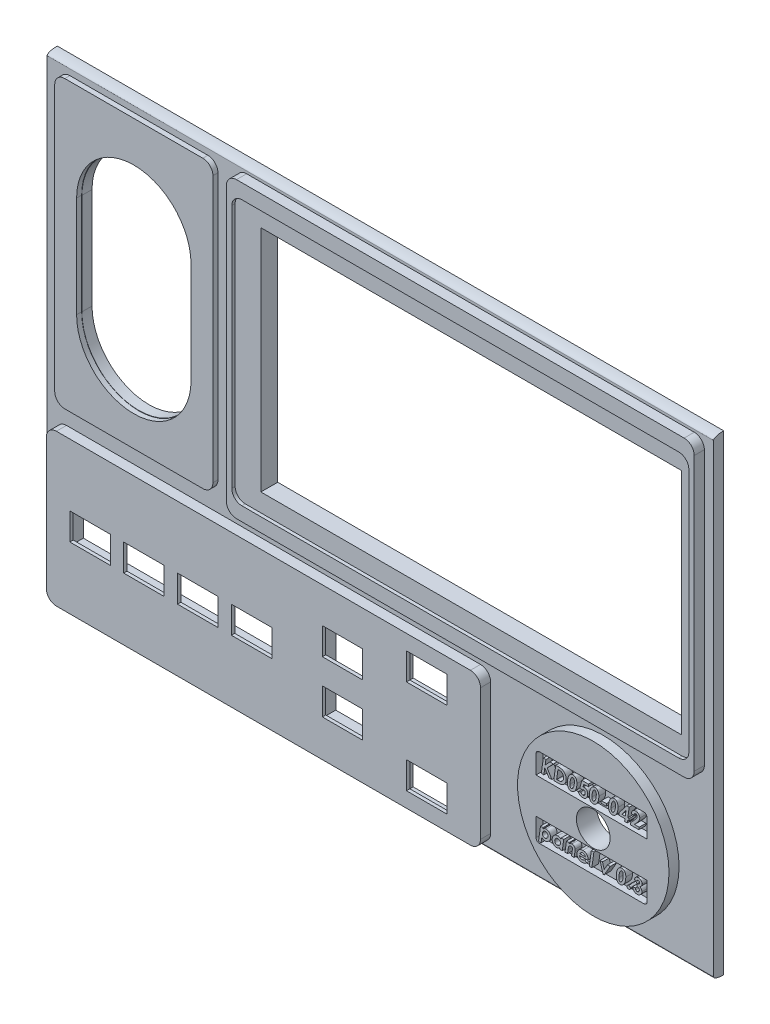
SolidWorks part; units mm, degrees
ref_plane "Front Plane" through (0, 0, 0) normal (0, 0, 1) x (1, 0, 0)
ref_plane "Top Plane" through (0, 0, 0) normal (0, 1, 0) x (1, 0, 0)
ref_plane "Right Plane" through (0, 0, 0) normal (1, 0, 0) x (0, 0, -1)
sketch "Sketch1" plane through (0, 0, 0) normal (0, 0, 1) x (1, 0, 0)
  line L1 (99, -70) -> (-99, -70)
  line L2 (99, -70) -> (99, 70)
  line L3 (99, 70) -> (-99, 70)
  line L4 (-99, -70) -> (-99, 70)
  line L5 (99, -70) -> (-99, 70) construction
  line L6 (99, 70) -> (-99, -70) construction
  point P0 (0, 0)
  dimension "D1" = 198
  dimension "D2" = 140
extrude "main_body" add sketch "Sketch1" along normal blind 3
fillet "long_corners" radius 3 2 edges at (0, 70, 3) (0, -70, 3) second distance 1 first distance on face at (0, 70, 1.5) first distance on face at (0, -70, 1.5)
sketch "Sketch2" plane through (0, 0, 3) normal (0, 0, 1) x (1, 0, 0)
  line L0 (-99, 24.75) -> (99, 24.75) construction
  line L1 (-99, 69) -> (-99, -69) construction
  line L2 (99, -69) -> (99, 69) construction
  line L3 (99, 69) -> (-99, 69) construction
  line L4 (-48.25, -17.75) -> (-95.25, -17.75)
  line L5 (-48.25, -17.75) -> (-48.25, 67.25)
  line L6 (-48.25, 67.25) -> (-95.25, 67.25)
  line L7 (-95.25, -17.75) -> (-95.25, 67.25)
  line L8 (-48.25, -17.75) -> (-95.25, 67.25) construction
  line L9 (-48.25, 67.25) -> (-95.25, -17.75) construction
  point P6 (-71.75, 24.75)
  dimension "D1" = 85
  dimension "D2" = 47
  dimension "D3" = 27.25
  dimension "D4" = 44.25
extrude "speaker" add sketch "Sketch2" along normal blind 1.5
fillet "speaker_corners" radius 3 4 edges at (-95.25, 67.25, 3.75) (-95.25, -17.75, 3.75) (-48.25, -17.75, 3.75) (-48.25, 67.25, 3.75)
sketch "Sketch19" plane through (0, 0, 4.5) normal (0, 0, 1) x (1, 0, 0)
  line L0 (-71.75, 67.25) -> (-71.75, -17.75) construction
  line L1 (-51.25, 67.25) -> (-92.25, 67.25) construction
  line L2 (-92.25, -17.75) -> (-51.25, -17.75) construction
  line L3 (-71.75, 8.25) -> (-71.75, 38.25) construction
  line L4 (-95.25, 64.25) -> (-95.25, -14.75) construction
  line L5 (-95.25, 24.75) -> (-48.25, 24.75) construction
  line L6 (-48.25, -14.75) -> (-48.25, 64.25) construction
  line L7 (-88.75, 8.25) -> (-88.75, 38.25)
  line L8 (-54.75, 8.25) -> (-54.75, 38.25)
  arc A0 (-88.75, 8.25) -> (-54.75, 8.25) centre (-71.75, 8.25) ccw
  arc A1 (-54.75, 38.25) -> (-88.75, 38.25) centre (-71.75, 38.25) ccw
  point P14 (-71.75, 23.25)
  point P19 (-71.75, -8.75)
  point P20 (-71.75, 55.25)
  dimension "D2" = 64
  dimension "D1" = 34
  dimension "D3" = 12
extrude "speaker_cut" cut sketch "Sketch19" against normal through all
sketch "Sketch21" plane through (0, 0, 0) normal (0, 0, -1) x (-1, 0, 0)
  line L0 (71.75, -8.75) -> (71.75, 55.25) construction
  line L2 (54.75, 8.25) -> (54.75, 38.25) construction
  line L3 (54.75, 23.25) -> (88.75, 23.25) construction
  line L4 (88.75, 38.25) -> (88.75, 8.25) construction
  line L5 (50.25, 59.25) -> (93.25, 59.25)
  line L6 (50.25, 59.25) -> (50.25, -12.75)
  line L7 (50.25, -12.75) -> (93.25, -12.75)
  line L8 (93.25, 59.25) -> (93.25, -12.75)
  line L9 (50.25, 59.25) -> (93.25, -12.75) construction
  line L10 (50.25, -12.75) -> (93.25, 59.25) construction
  arc A0 (54.75, 8.25) -> (88.75, 8.25) centre (71.75, 8.25) ccw construction
  arc A1 (88.75, 38.25) -> (54.75, 38.25) centre (71.75, 38.25) ccw construction
  point P14 (71.75, 23.25)
  dimension "D1" = 43
  dimension "D2" = 72
extrude "speaker_slot" cut sketch "Sketch21" against normal blind 3
sketch "Sketch36" plane through (0, 0, 3) normal (0, 0, -1) x (-1, 0, 0)
  line L0 (50.25, 23.25) -> (93.25, 23.25) construction
  line L1 (50.25, 59.25) -> (50.25, -12.75) construction
  line L2 (71.75, 8.2639) -> (71.75, 38.2361) construction
  line L3 (71.75, 8.2639) -> (71.75, 38.2361) construction
  line L4 (93.25, -12.75) -> (93.25, 59.25) construction
  line L5 (50.25, 59.25) -> (50.25, -12.75) construction
  line L6 (54.8316, 8.2639) -> (54.8316, 38.2361)
  line L9 (88.6684, 8.2639) -> (88.6684, 38.2361)
  line L10 (54.25, 8.2639) -> (54.25, 38.2361)
  line L11 (89.25, 8.2639) -> (89.25, 38.2361)
  line L12 (93.25, 59.25) -> (50.25, 59.25) construction
  line L13 (71.75, 59.25) -> (71.75, -12.75) construction
  line L14 (50.25, -12.75) -> (93.25, -12.75) construction
  line L23 (50.25, 57.25) -> (93.25, 57.25)
  line L25 (50.25, 57.25) -> (50.25, 56.75)
  line L26 (93.25, -0.25) -> (87.75, -0.25)
  line L27 (50.25, 56.75) -> (93.25, 56.75)
  line L28 (93.25, 57.25) -> (93.25, 56.75)
  line L37 (93.25, -12.75) -> (93.25, 59.25) construction
  line L38 (93.25, -0.25) -> (93.25, 0.25)
  line L39 (93.25, 0.25) -> (87.75, 0.25)
  line L48 (93.25, -10.75) -> (50.25, -10.75)
  line L49 (93.25, -10.75) -> (93.25, -10.25)
  line L50 (93.25, -10.25) -> (50.25, -10.25)
  line L51 (50.25, -10.75) -> (50.25, -10.25)
  line L52 (93.25, 46.75) -> (87.75, 46.75)
  line L53 (93.25, 46.75) -> (93.25, 46.25)
  line L54 (93.25, 46.25) -> (87.75, 46.25)
  line L55 (87.75, 46.75) -> (87.75, 46.25)
  line L56 (93.25, 35.25) -> (89.75, 35.25)
  line L57 (93.25, 35.25) -> (93.25, 34.75)
  line L58 (93.25, 34.75) -> (89.75, 34.75)
  line L59 (89.75, 35.25) -> (89.75, 34.75)
  line L60 (93.25, 23.25) -> (89.75, 23.25)
  line L61 (93.25, 23.25) -> (93.25, 23.75)
  line L62 (93.25, 23.75) -> (89.75, 23.75)
  line L63 (89.75, 23.25) -> (89.75, 23.75)
  line L64 (93.25, 10.75) -> (89.75, 10.75)
  line L65 (93.25, 10.75) -> (93.25, 11.25)
  line L66 (93.25, 11.25) -> (89.75, 11.25)
  line L67 (89.75, 10.75) -> (89.75, 11.25)
  line L68 (87.75, -0.25) -> (87.75, 0.25)
  line L69 (93.25, -5.25) -> (83.25, -5.25)
  line L70 (93.25, -5.25) -> (93.25, -5.75)
  line L71 (93.25, -5.75) -> (83.25, -5.75)
  line L72 (83.25, -5.25) -> (83.25, -5.75)
  line L73 (93.25, 52.25) -> (83.25, 52.25)
  line L74 (93.25, 52.25) -> (93.25, 51.75)
  line L75 (93.25, 51.75) -> (83.25, 51.75)
  line L76 (83.25, 52.25) -> (83.25, 51.75)
  line L77 (50.25, 52.25) -> (60.25, 52.25)
  line L78 (50.25, 52.25) -> (50.25, 51.75)
  line L79 (50.25, 51.75) -> (60.25, 51.75)
  line L80 (60.25, 52.25) -> (60.25, 51.75)
  line L81 (50.25, 46.75) -> (55.75, 46.75)
  line L82 (50.25, 46.75) -> (50.25, 46.25)
  line L83 (50.25, 46.25) -> (55.75, 46.25)
  line L84 (55.75, 46.75) -> (55.75, 46.25)
  line L85 (50.25, 35.25) -> (53.75, 35.25)
  line L86 (50.25, 35.25) -> (50.25, 34.75)
  line L87 (50.25, 34.75) -> (53.75, 34.75)
  line L88 (53.75, 35.25) -> (53.75, 34.75)
  line L89 (50.25, 23.25) -> (53.75, 23.25)
  line L90 (50.25, 23.25) -> (50.25, 23.75)
  line L91 (50.25, 23.75) -> (53.75, 23.75)
  line L92 (53.75, 23.25) -> (53.75, 23.75)
  line L93 (50.25, 10.25) -> (53.75, 10.25)
  line L94 (50.25, 10.25) -> (50.25, 10.75)
  line L95 (50.25, 10.75) -> (53.75, 10.75)
  line L96 (53.75, 10.25) -> (53.75, 10.75)
  line L97 (50.25, -0.25) -> (55.75, -0.25)
  line L98 (50.25, -0.25) -> (50.25, 0.25)
  line L99 (50.25, 0.25) -> (55.75, 0.25)
  line L100 (55.75, -0.25) -> (55.75, 0.25)
  line L101 (50.25, -5.25) -> (60.25, -5.25)
  line L102 (50.25, -5.25) -> (50.25, -5.75)
  line L103 (50.25, -5.75) -> (60.25, -5.75)
  line L104 (60.25, -5.25) -> (60.25, -5.75)
  arc A0 (54.25, 8.2639) -> (89.25, 8.2639) centre (71.75, 8.2639) ccw
  arc A1 (89.25, 38.2361) -> (54.25, 38.2361) centre (71.75, 38.2361) ccw
  arc A4 (54.8316, 8.2639) -> (88.6684, 8.2639) centre (71.75, 8.2639) ccw
  arc A5 (88.6684, 38.2361) -> (54.8316, 38.2361) centre (71.75, 38.2361) ccw
  point P6 (71.75, 23.25)
  point P22 (71.75, 23.25)
  point P31 (89.25, 23.25)
  point P32 (71.75, 55.1546)
  point P33 (71.75, -8.6546)
  point P95 (52, 35.25)
  point P96 (55.25, 51.75)
  point P97 (91.5, 10.75)
  dimension "D48" = 0.5816
  dimension "D1" = 33.8368
  dimension "D2" = 35
  dimension "D3" = 63.8091
  dimension "D4" = 0.5
  dimension "D5" = 0.5
  dimension "D6" = 0.5
  dimension "D7" = 0.5
  dimension "D8" = 0.5
  dimension "D9" = 11
  dimension "D10" = 11
  dimension "D11" = 5
  dimension "D12" = 4.5
  dimension "D13" = 10
  dimension "D14" = 5.5
  dimension "D15" = 3.5
  dimension "D16" = 3.5
  dimension "D17" = 0.5
  dimension "D18" = 0.5
  dimension "D19" = 0.5
  dimension "D20" = 0.5
  dimension "D21" = 11
  dimension "D22" = 11
  dimension "D23" = 5
  dimension "D24" = 10
  dimension "D25" = 5.5
  dimension "D26" = 3.5
  dimension "D27" = 3.5
  dimension "D28" = 0.5
  dimension "D29" = 0.5
  dimension "D30" = 0.5
  dimension "D31" = 0.5
  dimension "D32" = 0.5
  dimension "D33" = 0.5
  dimension "D34" = 0.5
  dimension "D35" = 12
  dimension "D36" = 10.5
  dimension "D37" = 5.5
  dimension "D38" = 5
  dimension "D39" = 4.5
  dimension "D40" = 3.5
  dimension "D41" = 10
  dimension "D42" = 4.5
  dimension "D43" = 5
  dimension "D44" = 10
  dimension "D45" = 3.5
  dimension "D46" = 5.5
  dimension "D47" = 10
extrude "speaker_print_support" add sketch "Sketch36" along normal blind 3
sketch "Sketch3" plane through (0, 0, 3) normal (0, 0, 1) x (1, 0, 0)
  line L0 (-99, 24.625) -> (99, 24.625) construction
  line L1 (-99, 69) -> (-99, -69) construction
  line L2 (99, -69) -> (99, 69) construction
  line L4 (-48.25, -14.75) -> (-48.25, 64.25) construction
  line L5 (96.25, -19) -> (-42.75, -19)
  line L6 (96.25, -19) -> (96.25, 68.25)
  line L7 (96.25, 68.25) -> (-42.75, 68.25)
  line L8 (-42.75, -19) -> (-42.75, 68.25)
  line L9 (96.25, -19) -> (-42.75, 68.25) construction
  line L10 (96.25, 68.25) -> (-42.75, -19) construction
  line L11 (99, 70) -> (-99, 70) construction
  point P8 (26.75, 24.625)
  dimension "D1" = 1.75
  dimension "D2" = 87.25
  dimension "D3" = 139
  dimension "D4" = 2.75
  dimension "D5" = 5.5
extrude "lcd" add sketch "Sketch3" along normal blind 3
fillet "lcd_corners" radius 3 4 edges at (96.25, -19, 4.5) (-42.75, -19, 4.5) (96.25, 68.25, 4.5) (-42.75, 68.25, 4.5)
sketch "Sketch9" plane through (0, 0, 6) normal (0, 0, 1) x (1, 0, 0)
  line L0 (-42.75, 24.5) -> (96.25, 24.5) construction
  line L1 (-42.75, 65.25) -> (-42.75, -16) construction
  line L2 (96.25, -16) -> (96.25, 65.25) construction
  line L3 (-39.75, -19) -> (93.25, -19) construction
  line L4 (94.65, -14.875) -> (-41.15, -14.875)
  line L5 (94.65, -14.875) -> (94.65, 63.875)
  line L6 (94.65, 63.875) -> (-41.15, 63.875)
  line L7 (-41.15, -14.875) -> (-41.15, 63.875)
  line L8 (94.65, -14.875) -> (-41.15, 63.875) construction
  line L9 (94.65, 63.875) -> (-41.15, -14.875) construction
  line L10 (93.25, 68.25) -> (-39.75, 68.25) construction
  line L11 (96.25, -16) -> (96.25, 65.25) construction
  point P6 (26.75, 24.5)
  dimension "D1" = 135.8
  dimension "D2" = 78.75
  dimension "D3" = 1.6
  dimension "D4" = 4.125
  dimension "D5" = 4.375
  dimension "D6" = 1.6
extrude "lcd_front" cut sketch "Sketch9" against normal blind 1
fillet "lcd_front_corners" radius 3 4 edges at (94.65, -14.875, 5.5) (94.65, 63.875, 5.5) (-41.15, 63.875, 5.5) (-41.15, -14.875, 5.5)
sketch "Sketch10" plane through (0, 0, 0) normal (0, 0, -1) x (-1, 0, 0)
  line L0 (-94.65, -11.875) -> (-94.65, 60.875) construction
  line L1 (-91.65, 63.875) -> (38.15, 63.875) construction
  line L2 (41.15, 63.875) -> (41.15, -14.875) construction
  line L3 (-94.65, 63.875) -> (41.15, 63.875) construction
  line L4 (33.5, -9.5) -> (-91.5, -9.5)
  line L5 (33.5, -9.5) -> (33.5, 58.5)
  line L6 (33.5, 58.5) -> (-91.5, 58.5)
  line L7 (-91.5, -9.5) -> (-91.5, 58.5)
  line L8 (-91.5, -9.5) -> (33.5, 58.5) construction
  line L9 (-91.5, 58.5) -> (33.5, -9.5) construction
  line L10 (-99, -70) -> (-99, 70) construction
  line L11 (-99, 70) -> (99, 70) construction
  line L13 (38.15, -14.875) -> (-91.65, -14.875) construction
  dimension "D1" = 125
  dimension "D2" = 68
  dimension "D3" = 7.5
  dimension "D4" = 7.65
  dimension "D5" = 11.5
  dimension "D6" = 5.375
  dimension "D7" = 3.15
  dimension "D8" = 5.375
  dimension "D9" = 5.375
extrude "lcd_back" cut sketch "Sketch10" against normal through all
sketch "Sketch4" plane through (0, 0, 3) normal (0, 0, 1) x (1, 0, 0)
  line L0 (-99, -45.75) -> (99, -45.75) construction
  line L1 (-99, 69) -> (-99, -69) construction
  line L2 (99, -69) -> (99, 69) construction
  line L4 (-92.25, -17.75) -> (-51.25, -17.75) construction
  line L5 (32.75, -68.25) -> (-96.25, -68.25)
  line L6 (32.75, -68.25) -> (32.75, -23.25)
  line L7 (32.75, -23.25) -> (-96.25, -23.25)
  line L8 (-96.25, -68.25) -> (-96.25, -23.25)
  line L9 (32.75, -68.25) -> (-96.25, -23.25) construction
  line L10 (32.75, -23.25) -> (-96.25, -68.25) construction
  line L11 (-99, -70) -> (99, -70) construction
  point P8 (-31.75, -45.75)
  dimension "D1" = 1.75
  dimension "D2" = 129
  dimension "D3" = 45
  dimension "D4" = 2.75
  dimension "D5" = 5.5
extrude "keypad" add sketch "Sketch4" along normal blind 3
fillet "keypad_corners" radius 3 4 edges at (-96.25, -68.25, 4.5) (32.75, -68.25, 4.5) (32.75, -23.25, 4.5) (-96.25, -23.25, 4.5)
sketch "Sketch25" plane through (0, 0, 6) normal (0, 0, 1) x (1, 0, 0)
  line L0 (-96.25, -30.25) -> (32.75, -30.25) construction
  line L1 (29.75, -23.25) -> (-93.25, -23.25) construction
  line L2 (-93.25, -68.25) -> (29.75, -68.25) construction
  line L3 (-77, -23.25) -> (-77, -68.25) construction
  line L5 (-35.4, -64) -> (32.75, -64) construction
  line L6 (-96.25, -26.25) -> (-96.25, -65.25) construction
  line L11 (32.75, -65.25) -> (32.75, -26.25) construction
  line L12 (-58.7, -23.25) -> (-58.7, -68.25) construction
  line L13 (-96.25, -40.25) -> (32.75, -40.25) construction
  line L14 (29.75, -23.25) -> (-93.25, -23.25) construction
  line L15 (-40.4, -23.25) -> (-40.4, -68.25) construction
  line L16 (-93.25, -68.25) -> (29.75, -68.25) construction
  line L17 (-72, -34) -> (-82, -34)
  line L18 (-22.1, -23.25) -> (-22.1, -68.25) construction
  line L19 (-96.25, -50.25) -> (32.75, -50.25) construction
  line L20 (-3.8, -23.25) -> (-3.8, -68.25) construction
  line L21 (-72, -34) -> (-72, -26.5)
  line L22 (14.5, -23.25) -> (14.5, -68.25) construction
  line L23 (-96.25, -26.25) -> (-96.25, -65.25) construction
  line L24 (-96.25, -60.25) -> (32.75, -60.25) construction
  line L25 (-72, -26.5) -> (-82, -26.5)
  line L26 (-82, -34) -> (-82, -26.5)
  line L27 (-72, -34) -> (-82, -26.5) construction
  line L28 (-72, -26.5) -> (-82, -34) construction
  line L29 (-72, -44) -> (-82, -44)
  line L30 (-72, -44) -> (-72, -36.5)
  line L31 (-72, -36.5) -> (-82, -36.5)
  line L32 (-82, -44) -> (-82, -36.5)
  line L33 (-72, -44) -> (-82, -36.5) construction
  line L34 (-72, -36.5) -> (-82, -44) construction
  line L35 (-72, -54) -> (-82, -54)
  line L36 (-72, -54) -> (-72, -46.5)
  line L37 (-72, -46.5) -> (-82, -46.5)
  line L38 (-82, -54) -> (-82, -46.5)
  line L39 (-72, -54) -> (-82, -46.5) construction
  line L40 (-72, -46.5) -> (-82, -54) construction
  line L41 (-72, -64) -> (-82, -64)
  line L42 (-72, -64) -> (-72, -56.5)
  line L43 (-72, -56.5) -> (-82, -56.5)
  line L44 (-82, -64) -> (-82, -56.5)
  line L45 (-72, -64) -> (-82, -56.5) construction
  line L46 (-72, -56.5) -> (-82, -64) construction
  line L47 (-53.7, -34) -> (-63.7, -34)
  line L48 (-53.7, -34) -> (-53.7, -26.5)
  line L49 (-53.7, -26.5) -> (-63.7, -26.5)
  line L50 (-63.7, -34) -> (-63.7, -26.5)
  line L51 (-53.7, -34) -> (-63.7, -26.5) construction
  line L52 (-53.7, -26.5) -> (-63.7, -34) construction
  line L53 (-53.7, -44) -> (-63.7, -44)
  line L54 (-53.7, -44) -> (-53.7, -36.5)
  line L55 (-53.7, -36.5) -> (-63.7, -36.5)
  line L56 (-63.7, -44) -> (-63.7, -36.5)
  line L57 (-53.7, -44) -> (-63.7, -36.5) construction
  line L58 (-53.7, -36.5) -> (-63.7, -44) construction
  line L59 (-53.7, -54) -> (-63.7, -54)
  line L60 (-53.7, -54) -> (-53.7, -46.5)
  line L61 (-53.7, -46.5) -> (-63.7, -46.5)
  line L62 (-63.7, -54) -> (-63.7, -46.5)
  line L63 (-53.7, -54) -> (-63.7, -46.5) construction
  line L64 (-53.7, -46.5) -> (-63.7, -54) construction
  line L65 (-53.7, -64) -> (-63.7, -64)
  line L66 (-53.7, -64) -> (-53.7, -56.5)
  line L67 (-53.7, -56.5) -> (-63.7, -56.5)
  line L68 (-63.7, -64) -> (-63.7, -56.5)
  line L69 (-53.7, -64) -> (-63.7, -56.5) construction
  line L70 (-53.7, -56.5) -> (-63.7, -64) construction
  line L71 (-35.4, -34) -> (-45.4, -34)
  line L72 (-35.4, -34) -> (-35.4, -26.5)
  line L73 (-35.4, -26.5) -> (-45.4, -26.5)
  line L74 (-45.4, -34) -> (-45.4, -26.5)
  line L75 (-35.4, -34) -> (-45.4, -26.5) construction
  line L76 (-35.4, -26.5) -> (-45.4, -34) construction
  line L77 (-35.4, -44) -> (-45.4, -44)
  line L78 (-35.4, -44) -> (-35.4, -36.5)
  line L79 (-35.4, -36.5) -> (-45.4, -36.5)
  line L80 (-45.4, -44) -> (-45.4, -36.5)
  line L81 (-35.4, -44) -> (-45.4, -36.5) construction
  line L82 (-35.4, -36.5) -> (-45.4, -44) construction
  line L83 (-35.4, -54) -> (-45.4, -54)
  line L84 (-35.4, -54) -> (-35.4, -46.5)
  line L85 (-35.4, -46.5) -> (-45.4, -46.5)
  line L86 (-45.4, -54) -> (-45.4, -46.5)
  line L87 (-35.4, -54) -> (-45.4, -46.5) construction
  line L88 (-35.4, -46.5) -> (-45.4, -54) construction
  line L89 (-35.4, -64) -> (-45.4, -64)
  line L90 (-35.4, -64) -> (-35.4, -56.5)
  line L91 (-35.4, -56.5) -> (-45.4, -56.5)
  line L92 (-45.4, -64) -> (-45.4, -56.5)
  line L93 (-35.4, -64) -> (-45.4, -56.5) construction
  line L94 (-35.4, -56.5) -> (-45.4, -64) construction
  line L95 (-17.1, -34) -> (-27.1, -34)
  line L96 (-17.1, -34) -> (-17.1, -26.5)
  line L97 (-17.1, -26.5) -> (-27.1, -26.5)
  line L98 (-27.1, -34) -> (-27.1, -26.5)
  line L99 (-17.1, -34) -> (-27.1, -26.5) construction
  line L100 (-17.1, -26.5) -> (-27.1, -34) construction
  line L101 (-17.1, -44) -> (-27.1, -44)
  line L102 (-17.1, -44) -> (-17.1, -36.5)
  line L103 (-17.1, -36.5) -> (-27.1, -36.5)
  line L104 (-27.1, -44) -> (-27.1, -36.5)
  line L105 (-17.1, -44) -> (-27.1, -36.5) construction
  line L106 (-17.1, -36.5) -> (-27.1, -44) construction
  line L111 (-17.1, -54) -> (-27.1, -54)
  line L112 (-17.1, -54) -> (-17.1, -46.5)
  line L113 (-17.1, -46.5) -> (-27.1, -46.5)
  line L114 (-27.1, -54) -> (-27.1, -46.5)
  line L115 (-17.1, -54) -> (-27.1, -46.5) construction
  line L116 (-17.1, -46.5) -> (-27.1, -54) construction
  line L117 (-17.1, -64) -> (-27.1, -64)
  line L118 (-17.1, -64) -> (-17.1, -56.5)
  line L119 (-17.1, -56.5) -> (-27.1, -56.5)
  line L120 (-27.1, -64) -> (-27.1, -56.5)
  line L121 (-17.1, -64) -> (-27.1, -56.5) construction
  line L122 (-17.1, -56.5) -> (-27.1, -64) construction
  line L127 (1.2, -34) -> (-8.8, -34)
  line L128 (1.2, -34) -> (1.2, -26.5)
  line L129 (1.2, -26.5) -> (-8.8, -26.5)
  line L130 (-8.8, -34) -> (-8.8, -26.5)
  line L131 (1.2, -34) -> (-8.8, -26.5) construction
  line L132 (1.2, -26.5) -> (-8.8, -34) construction
  line L133 (19.5, -34) -> (9.5, -34)
  line L134 (19.5, -34) -> (19.5, -26.5)
  line L135 (19.5, -26.5) -> (9.5, -26.5)
  line L136 (9.5, -34) -> (9.5, -26.5)
  line L137 (19.5, -34) -> (9.5, -26.5) construction
  line L138 (19.5, -26.5) -> (9.5, -34) construction
  line L139 (1.2, -44) -> (-8.8, -44)
  line L140 (1.2, -44) -> (1.2, -36.5)
  line L141 (1.2, -36.5) -> (-8.8, -36.5)
  line L142 (-8.8, -44) -> (-8.8, -36.5)
  line L143 (1.2, -44) -> (-8.8, -36.5) construction
  line L144 (1.2, -36.5) -> (-8.8, -44) construction
  line L145 (19.5, -44) -> (9.5, -44)
  line L146 (19.5, -44) -> (19.5, -36.5)
  line L147 (19.5, -36.5) -> (9.5, -36.5)
  line L148 (9.5, -44) -> (9.5, -36.5)
  line L149 (19.5, -44) -> (9.5, -36.5) construction
  line L150 (19.5, -36.5) -> (9.5, -44) construction
  line L151 (19.5, -54) -> (9.5, -54)
  line L152 (19.5, -54) -> (19.5, -46.5)
  line L153 (19.5, -46.5) -> (9.5, -46.5)
  line L154 (9.5, -54) -> (9.5, -46.5)
  line L155 (19.5, -54) -> (9.5, -46.5) construction
  line L156 (19.5, -46.5) -> (9.5, -54) construction
  line L157 (19.5, -64) -> (9.5, -64)
  line L158 (19.5, -64) -> (19.5, -56.5)
  line L159 (19.5, -56.5) -> (9.5, -56.5)
  line L160 (9.5, -64) -> (9.5, -56.5)
  line L161 (19.5, -64) -> (9.5, -56.5) construction
  line L162 (19.5, -56.5) -> (9.5, -64) construction
  line L163 (1.2, -64) -> (-8.8, -64)
  line L164 (1.2, -64) -> (1.2, -46.5)
  line L165 (1.2, -46.5) -> (-8.8, -46.5)
  line L166 (-8.8, -64) -> (-8.8, -46.5)
  line L167 (1.2, -64) -> (-8.8, -46.5) construction
  line L168 (1.2, -46.5) -> (-8.8, -64) construction
  point P34 (-77, -30.25)
  point P39 (-77, -40.25)
  point P44 (-77, -50.25)
  point P49 (-77, -60.25)
  point P54 (-58.7, -30.25)
  point P59 (-58.7, -40.25)
  point P64 (-58.7, -50.25)
  point P69 (-58.7, -60.25)
  point P74 (-40.4, -30.25)
  point P79 (-40.4, -40.25)
  point P84 (-40.4, -50.25)
  point P89 (-40.4, -60.25)
  point P94 (-22.1, -30.25)
  point P99 (-22.1, -40.25)
  point P104 (-22.1, -50.25)
  point P109 (-22.1, -60.25)
  point P114 (-3.8, -30.25)
  point P119 (14.5, -30.25)
  point P124 (-3.8, -40.25)
  point P129 (14.5, -40.25)
  point P134 (14.5, -50.25)
  point P139 (14.5, -60.25)
  point P144 (-3.8, -55.25)
  dimension "D1" = 18.25
  dimension "D2" = 18.3
  dimension "D3" = 18.3
  dimension "D4" = 18.3
  dimension "D5" = 18.3
  dimension "D6" = 18.3
  dimension "D7" = 19.25
  dimension "D8" = 7
  dimension "D9" = 10
  dimension "D10" = 10
  dimension "D11" = 10
  dimension "D12" = 8
  dimension "D13" = 10
  dimension "D14" = 10
  dimension "D15" = 10
  dimension "D16" = 10
  dimension "D17" = 10
  dimension "D18" = 10
  dimension "D19" = 10
  dimension "D20" = 10
  dimension "D21" = 10
  dimension "D22" = 10
  dimension "D23" = 10
  dimension "D24" = 10
  dimension "D25" = 10
  dimension "D26" = 10
  dimension "D27" = 10
  dimension "D28" = 10
  dimension "D29" = 10
  dimension "D30" = 10
  dimension "D31" = 10
  dimension "D32" = 10
  dimension "D33" = 10
  dimension "D34" = 10
  dimension "D35" = 10
  dimension "D36" = 7.5
  dimension "D37" = 7.5
  dimension "D38" = 7.5
  dimension "D39" = 7.5
  dimension "D40" = 7.5
  dimension "D41" = 7.5
  dimension "D42" = 17.5
  dimension "D43" = 7.5
  dimension "D44" = 7.5
  dimension "D45" = 7.5
  dimension "D46" = 7.5
  dimension "D47" = 7.5
  dimension "D48" = 7.5
  dimension "D49" = 7.5
  dimension "D50" = 7.5
  dimension "D51" = 7.5
  dimension "D52" = 7.5
  dimension "D53" = 7.5
  dimension "D54" = 7.5
  dimension "D55" = 7.5
  dimension "D56" = 7.5
  dimension "D57" = 7.5
  dimension "D58" = 7.5
  dimension "D59" = 5
extrude "keypad_cuts_0.8" [suppressed] cut sketch "Sketch25" against normal through all
sketch "Sketch40" plane through (0, 0, 6) normal (0, 0, 1) x (1, 0, 0)
  line L0 (16.75, -23.25) -> (16.75, -68.25) construction
  line L1 (-8.25, -23.25) -> (-8.25, -68.25) construction
  line L2 (-67.25, -23.25) -> (-67.25, -68.25) construction
  line L3 (-96.25, -45.75) -> (32.75, -45.75) construction
  line L4 (-83.25, -23.25) -> (-83.25, -68.25) construction
  line L5 (29.75, -23.25) -> (-93.25, -23.25) construction
  line L6 (-93.25, -68.25) -> (29.75, -68.25) construction
  line L11 (-77.25, -49.75) -> (-89.25, -49.75)
  line L12 (-77.25, -49.75) -> (-77.25, -41.75)
  line L13 (-93.25, -68.25) -> (29.75, -68.25) construction
  line L14 (-77.25, -41.75) -> (-89.25, -41.75)
  line L15 (-89.25, -49.75) -> (-89.25, -41.75)
  line L16 (-35.25, -68.25) -> (-35.25, -23.25) construction
  line L18 (29.75, -23.25) -> (-93.25, -23.25) construction
  line L19 (-77.25, -49.75) -> (-89.25, -41.75) construction
  line L20 (-51.25, -68.25) -> (-51.25, -23.25) construction
  line L22 (-77.25, -41.75) -> (-89.25, -49.75) construction
  line L23 (-61.25, -49.75) -> (-73.25, -49.75)
  line L24 (-61.25, -49.75) -> (-61.25, -41.75)
  line L25 (-61.25, -41.75) -> (-73.25, -41.75)
  line L26 (-73.25, -49.75) -> (-73.25, -41.75)
  line L27 (-61.25, -49.75) -> (-73.25, -41.75) construction
  line L28 (-61.25, -41.75) -> (-73.25, -49.75) construction
  line L29 (-45.25, -49.75) -> (-57.25, -49.75)
  line L30 (-45.25, -49.75) -> (-45.25, -41.75)
  line L31 (-45.25, -41.75) -> (-57.25, -41.75)
  line L32 (-57.25, -49.75) -> (-57.25, -41.75)
  line L33 (-45.25, -49.75) -> (-57.25, -41.75) construction
  line L34 (-45.25, -41.75) -> (-57.25, -49.75) construction
  line L35 (-29.25, -49.75) -> (-41.25, -49.75)
  line L36 (-29.25, -49.75) -> (-29.25, -41.75)
  line L37 (-29.25, -41.75) -> (-41.25, -41.75)
  line L38 (-41.25, -49.75) -> (-41.25, -41.75)
  line L39 (-29.25, -49.75) -> (-41.25, -41.75) construction
  line L40 (-29.25, -41.75) -> (-41.25, -49.75) construction
  line L45 (-2.25, -41.75) -> (-14.25, -41.75)
  line L46 (-2.25, -41.75) -> (-2.25, -33.75)
  line L51 (-2.25, -33.75) -> (-14.25, -33.75)
  line L52 (-14.25, -41.75) -> (-14.25, -33.75)
  line L53 (22.75, -35.75) -> (10.75, -35.75)
  line L54 (22.75, -35.75) -> (22.75, -27.75)
  line L55 (22.75, -27.75) -> (10.75, -27.75)
  line L56 (10.75, -35.75) -> (10.75, -27.75)
  line L57 (22.75, -35.75) -> (10.75, -27.75) construction
  line L58 (22.75, -27.75) -> (10.75, -35.75) construction
  line L59 (22.75, -63.75) -> (10.75, -63.75)
  line L60 (22.75, -63.75) -> (22.75, -55.75)
  line L61 (22.75, -55.75) -> (10.75, -55.75)
  line L62 (10.75, -63.75) -> (10.75, -55.75)
  line L63 (22.75, -63.75) -> (10.75, -55.75) construction
  line L64 (22.75, -55.75) -> (10.75, -63.75) construction
  line L69 (32.75, -65.25) -> (32.75, -26.25) construction
  line L70 (-2.25, -57.25) -> (-14.25, -57.25)
  line L75 (-2.25, -57.25) -> (-2.25, -49.25)
  line L76 (-2.25, -49.25) -> (-14.25, -49.25)
  line L77 (-2.25, -41.75) -> (-14.25, -33.75) construction
  line L78 (-2.25, -33.75) -> (-14.25, -41.75) construction
  line L85 (-14.25, -57.25) -> (-14.25, -49.25)
  line L86 (-2.25, -57.25) -> (-14.25, -49.25) construction
  line L87 (-2.25, -49.25) -> (-14.25, -57.25) construction
  line L88 (-96.25, -26.25) -> (-96.25, -65.25) construction
  line L89 (32.75, -65.25) -> (32.75, -26.25) construction
  line L93 (32.75, -59.75) -> (-96.25, -59.75) construction
  line L94 (-96.25, -31.75) -> (32.75, -31.75) construction
  line L95 (32.75, -31.75) -> (32.75, -37.75) construction
  line L96 (32.75, -37.75) -> (-96.25, -37.75) construction
  line L99 (-96.25, -26.25) -> (-96.25, -65.25) construction
  line L100 (-96.25, -53.75) -> (32.75, -53.75) construction
  point P18 (-83.25, -45.75)
  point P25 (-67.25, -45.75)
  point P30 (-51.25, -45.75)
  point P35 (-35.25, -45.75)
  point P40 (-8.25, -37.75)
  point P45 (-8.25, -53.25)
  point P50 (16.75, -31.75)
  point P55 (16.75, -59.75)
  point P71 (0, 0)
  point P75 (0, 0)
  point P76 (0, 0)
  point P81 (32.75, -53.25)
  dimension "D1" = 8
  dimension "D2" = 8
  dimension "D3" = 8
  dimension "D4" = 8
  dimension "D5" = 8
  dimension "D6" = 12
  dimension "D7" = 8
  dimension "D8" = 8
  dimension "D9" = 12
  dimension "D10" = 12
  dimension "D11" = 12
  dimension "D12" = 12
  dimension "D13" = 12
  dimension "D14" = 12
  dimension "D15" = 8
  dimension "D16" = 12
  dimension "D17" = 8
  dimension "D18" = 8
  dimension "D19" = 27
  dimension "D20" = 14
  dimension "D21" = 16
  dimension "D22" = 16
  dimension "D23" = 16
  dimension "D24" = 25
  dimension "D25" = 14
extrude "keypad_cuts_0.7" cut sketch "Sketch40" against normal through all
sketch "Sketch41" plane through (0, 0, 0) normal (0, 0, -1) x (-1, 0, 0)
  line L0 (-22.75, -27.75) -> (-10.75, -35.75) construction
  line L1 (-22.75, -55.75) -> (-10.75, -63.75) construction
  line L2 (8.25, -33.75) -> (8.25, -57.25) construction
  line L3 (-10.75, -63.75) -> (-22.75, -63.75) construction
  line L4 (29.25, -45.75) -> (89.25, -45.75) construction
  line L5 (29.25, -49.75) -> (29.25, -41.75) construction
  line L6 (89.25, -41.75) -> (89.25, -49.75) construction
  line L7 (-6.75, -39.75) -> (-26.75, -39.75)
  line L8 (2.25, -33.75) -> (14.25, -33.75) construction
  line L9 (-6.75, -39.75) -> (-6.75, -23.75)
  line L10 (91.25, -52.75) -> (27.25, -52.75)
  line L11 (-6.75, -23.75) -> (-26.75, -23.75)
  line L12 (14.25, -57.25) -> (2.25, -57.25) construction
  line L13 (-26.75, -39.75) -> (-26.75, -23.75)
  line L14 (-10.75, -55.75) -> (-22.75, -63.75) construction
  line L15 (-6.75, -39.75) -> (-26.75, -23.75) construction
  line L16 (-10.75, -35.75) -> (-22.75, -35.75) construction
  line L17 (-22.75, -35.75) -> (-22.75, -27.75) construction
  line L18 (-22.75, -35.75) -> (-10.75, -27.75) construction
  line L19 (-6.75, -23.75) -> (-26.75, -39.75) construction
  line L21 (-6.75, -67.75) -> (-26.75, -67.75)
  line L22 (16.25, -59.5) -> (0.25, -59.5)
  line L23 (-6.75, -67.75) -> (-6.75, -51.75)
  line L24 (91.25, -52.75) -> (91.25, -38.75)
  line L25 (-6.75, -51.75) -> (-26.75, -51.75)
  line L26 (91.25, -38.75) -> (27.25, -38.75)
  line L27 (-26.75, -67.75) -> (-26.75, -51.75)
  line L28 (27.25, -52.75) -> (27.25, -38.75)
  line L29 (-6.75, -67.75) -> (-26.75, -51.75) construction
  line L30 (91.25, -52.75) -> (27.25, -38.75) construction
  line L31 (-6.75, -51.75) -> (-26.75, -67.75) construction
  line L36 (16.25, -59.5) -> (16.25, -31.5)
  line L37 (16.25, -31.5) -> (0.25, -31.5)
  line L42 (0.25, -59.5) -> (0.25, -31.5)
  line L43 (16.25, -59.5) -> (0.25, -31.5) construction
  line L48 (91.25, -38.75) -> (27.25, -52.75) construction
  line L49 (16.25, -31.5) -> (0.25, -59.5) construction
  point P19 (59.25, -45.75)
  point P44 (8.25, -45.5)
  point P68 (-16.75, -59.75)
  point P69 (-16.75, -31.75)
  dimension "D1" = 20
  dimension "D2" = 20
  dimension "D3" = 16
  dimension "D4" = 16
  dimension "D5" = 16
  dimension "D6" = 28
  dimension "D7" = 64
  dimension "D8" = 14
extrude "keypad_back_0.7" cut sketch "Sketch41" against normal blind 5
sketch "Sketch5" plane through (0, 0, 3) normal (0, 0, 1) x (1, 0, 0)
  line L0 (32.75, -45.75) -> (99, -45.75) construction
  line L1 (32.75, -65.25) -> (32.75, -26.25) construction
  line L2 (99, -69) -> (99, 69) construction
  circle A0 centre (66.25, -45.75) radius 22.5
  dimension "D1" = 45
  dimension "D2" = 32.75
  dimension "D3" = 33.5
extrude "vfo" add sketch "Sketch5" along normal blind 3
sketch "Sketch7" plane through (0, 0, 6) normal (0, 0, 1) x (1, 0, 0)
  line L0 (43.75, -45.75) -> (88.75, -45.75) construction
  line L1 (66.25, -23.25) -> (66.25, -68.25) construction
  circle A0 centre (66.25, -45.75) radius 22.5 construction
  circle A1 centre (66.25, -45.75) radius 22.5 construction
  circle A2 centre (66.25, -45.75) radius 5
  dimension "D1" = 10
extrude "vfo_encoder_knob_cut" cut sketch "Sketch7" against normal through all
sketch "Sketch37" plane through (0, 0, 6) normal (0, 0, 1) x (1, 0, 0)
  line L1 (49.25, -51.05) -> (82.25, -51.05)
  line L2 (49.25, -51.05) -> (49.25, -57.55)
  line L3 (49.25, -57.55) -> (82.25, -57.55)
  line L4 (82.25, -51.05) -> (82.25, -57.55)
  line L5 (49.25, -33.95) -> (82.25, -33.95)
  line L6 (49.25, -33.95) -> (49.25, -40.45)
  line L7 (49.25, -40.45) -> (82.25, -40.45)
  line L8 (82.25, -33.95) -> (82.25, -40.45)
  circle A0 centre (66.25, -45.75) radius 5 construction
  dimension "D1" = 6.5
  dimension "D2" = 33
  dimension "D3" = 5.3
  dimension "D4" = 16
  dimension "D5" = 33
  dimension "D6" = 6.5
  dimension "D7" = 5.3
  dimension "D8" = 16
extrude "logo_cut" cut sketch "Sketch37" against normal blind 2
sketch "Sketch38" plane through (0, 0, 4) normal (0, 0, 1) x (1, 0, 0)
  line L0 (49.25, -33.95) -> (49.25, -40.45) construction
  line L1 (49.25, -40.45) -> (82.25, -40.45) construction
  text T0 "KD050-042" font "Century Gothic" height in points 16
  dimension "D1" = 1.4
  dimension "D2" = 1.2
extrude "logo_txt_lcd" add sketch "Sketch38" along normal blind 2 separate body
sketch "Sketch39" plane through (0, 0, 4) normal (0, 0, 1) x (1, 0, 0)
  line L0 (49.25, -51.05) -> (49.25, -57.55) construction
  line L1 (49.25, -57.55) -> (82.25, -57.55) construction
  text T0 "panel v 0.3\r\n" font "Century Gothic" height in points 16
  dimension "D1" = 0.7816
  dimension "D2" = 1.5336
extrude "logo_txt_ver" add sketch "Sketch39" along normal blind 2
fillet "logo_corners" radius 1 4 edges at (49.25, -33.95, 5) (82.25, -33.95, 5) (82.25, -57.55, 5) (49.25, -57.55, 5)
